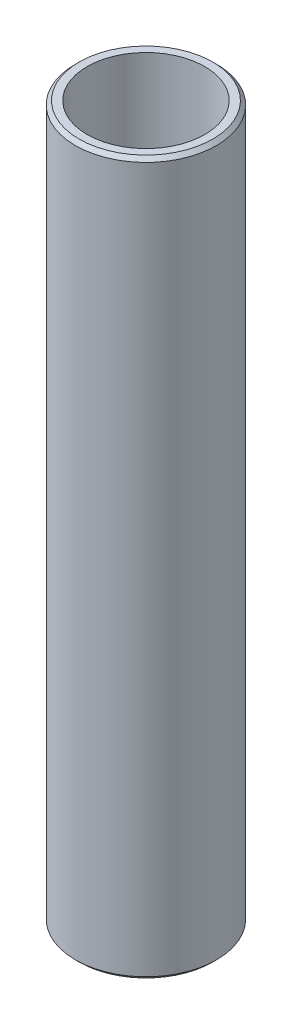
SolidWorks part; units mm, degrees
ref_plane "Front Plane" through (0, 0, 0) normal (0, 0, 1) x (1, 0, 0)
ref_plane "Top Plane" through (0, 0, 0) normal (0, 1, 0) x (1, 0, 0)
ref_plane "Right Plane" through (0, 0, 0) normal (1, 0, 0) x (0, 0, -1)
sketch "Sketch1" plane through (0, 0, 0) normal (0, 1, 0) x (1, 0, 0)
  circle A0 centre (0, 0) radius 47.5
  dimension "SHAFT_OD" = 95
extrude "Boss-Extrude1" add sketch "Sketch1" along normal blind 479.8571
sketch "Sketch2" plane through (0, 0, 0) normal (0, 1, 0) x (1, 0, 0)
  circle A0 centre (0, 0) radius 39.6369
  dimension "BORE_D" = 79.2738
extrude "Cut-Extrude1" cut sketch "Sketch2" along normal through all
chamfer "Chamfer1" distance 2.5134 angle 45 2 edges at (0, 479.8571, 47.5) (0, 0, 47.5)
